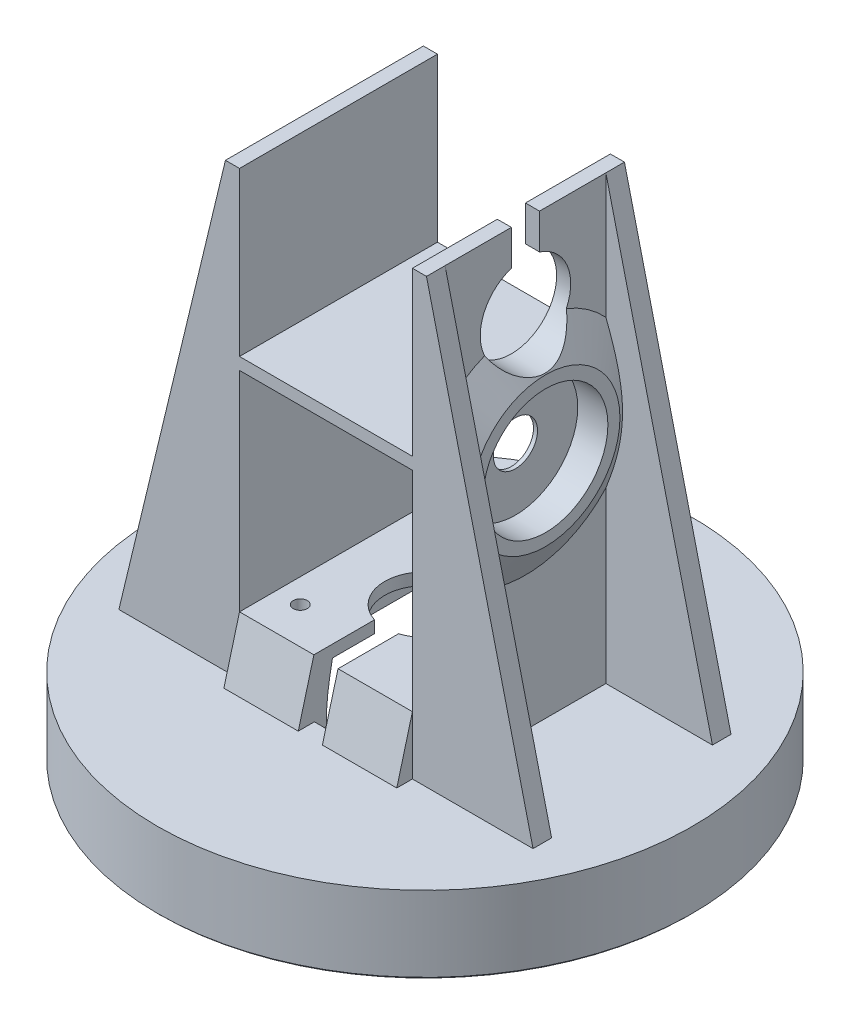
SolidWorks part; units mm, degrees
material "ABS"
ref_plane "Front Plane" through (0, 0, 0) normal (0, 0, 1) x (1, 0, 0)
ref_plane "Top Plane" through (0, 0, 0) normal (0, 1, 0) x (1, 0, 0)
ref_plane "Right Plane" through (0, 0, 0) normal (1, 0, 0) x (0, 0, -1)
sketch "Sketch1" plane through (0, 0, 0) normal (0, 1, 0) x (1, 0, 0)
  circle A0 centre (0, 0) radius 62.775 construction
  circle A1 centre (0, 0) radius 63.525
  circle A2 centre (0, 0) radius 66.525
  dimension "D1" = 125.55
  dimension "D2" = 0.75
  dimension "D3" = 3
extrude "Boss-Extrude1" add sketch "Sketch1" along normal blind 16.75
sketch "Sketch2" plane through (0, 16.75, 0) normal (0, 1, 0) x (1, 0, 0)
  circle A0 centre (0, 0) radius 66.525
  circle A1 centre (0, 0) radius 66.525 construction
extrude "Boss-Extrude2" add sketch "Sketch2" along normal blind 2.5
chamfer "Chamfer1" distance 0.5 angle 45 2 edges at (0, 0, 63.525) (0, 0, 66.525)
sketch "Sketch3" plane through (0, 16.75, 0) normal (0, -1, 0) x (1, 0, 0)
  line L0 (0, 37.5) -> (0, -37.5) construction
  line L1 (37.5, 0) -> (-37.5, 0) construction
  circle A0 centre (0, 37.5) radius 3
  circle A1 centre (37.5, 0) radius 3
  circle A2 centre (0, -37.5) radius 3
  circle A3 centre (-37.5, 0) radius 3
  point P8 (0, 0)
  point P9 (57.1447, 0)
  point P11 (0, 0)
  point P12 (0, 0)
  dimension "D1" = 6
  dimension "D2" = 75
extrude "Boss-Extrude3" add sketch "Sketch3" along normal blind 4
chamfer "Chamfer2" distance 0.5 angle 45 4 edges at (37.5, 16.75, 3) (0, 16.75, -34.5) (-37.5, 16.75, 3) (0, 16.75, 40.5)
sketch "Sketch4" plane through (0, 19.25, 0) normal (0, 1, 0) x (1, 0, 0)
  line L1 (-15.5, -15.5) -> (15.5, -15.5) construction
  line L2 (-15.5, -15.5) -> (-15.5, 15.5) construction
  line L3 (-15.5, 15.5) -> (15.5, 15.5) construction
  line L4 (15.5, -15.5) -> (15.5, 15.5) construction
  line L5 (-15.5, -15.5) -> (15.5, 15.5) construction
  line L6 (-15.5, 15.5) -> (15.5, -15.5) construction
  line L7 (-21.5, -21.5) -> (21.5, -21.5)
  line L8 (-21.5, -21.5) -> (-21.5, 21.5)
  line L9 (-21.5, 21.5) -> (21.5, 21.5)
  line L10 (21.5, -21.5) -> (21.5, 21.5)
  line L11 (-21.5, -21.5) -> (21.5, 21.5) construction
  line L12 (-21.5, 21.5) -> (21.5, -21.5) construction
  point P1 (0, 0)
  point P6 (0, 0)
  dimension "D1" = 31
  dimension "D2" = 6
extrude "Cut-Extrude1" cut sketch "Sketch4" against normal up to next
sketch "Sketch5" plane through (0, 19.25, 0) normal (0, 1, 0) x (1, 0, 0)
  line L0 (-21.5, 21.5) -> (21.5, 21.5)
  line L1 (-21.5, 21.5) -> (-21.5, 24.5)
  line L2 (21.5, 21.5) -> (21.5, 24.5)
  line L3 (-21.5, 24.5) -> (21.5, 24.5)
  line L4 (21.5, -21.5) -> (-21.5, -21.5)
  line L5 (21.5, -21.5) -> (21.5, -24.5)
  line L6 (-21.5, -21.5) -> (-21.5, -24.5)
  line L7 (21.5, -24.5) -> (-21.5, -24.5)
  dimension "D1" = 3
extrude "Boss-Extrude4" add sketch "Sketch5" along normal blind 14.5
sketch "Sketch6" plane through (0, 33.75, 0) normal (0, 1, 0) x (1, 0, 0)
  line L0 (-21.5, 24.5) -> (-21.5, -24.5)
  line L1 (-21.5, 24.5) -> (21.5, 24.5)
  line L2 (-21.5, -24.5) -> (21.5, -24.5)
  line L3 (21.5, 24.5) -> (21.5, -24.5)
  line L4 (-21.5, -24.5) -> (21.5, -24.5) construction
  point P0 (15.586, -24.5)
extrude "Boss-Extrude5" add sketch "Sketch6" against normal blind 3
sketch "Sketch7" plane through (0, 33.75, 0) normal (0, 1, 0) x (1, 0, 0)
  line L0 (-3, -24.5) -> (-3, -9.5394)
  line L1 (-15.5, -15.5) -> (15.5, -15.5) construction
  line L2 (-15.5, -15.5) -> (-15.5, 15.5) construction
  line L3 (-15.5, 15.5) -> (15.5, 15.5) construction
  line L4 (15.5, -15.5) -> (15.5, 15.5) construction
  line L5 (-15.5, -15.5) -> (15.5, 15.5) construction
  line L6 (-15.5, 15.5) -> (15.5, -15.5) construction
  line L8 (3, -9.5394) -> (3, -24.5)
  line L9 (3, -24.5) -> (-3, -24.5)
  line L10 (-21.5, -24.5) -> (21.5, -24.5) construction
  circle A0 centre (15.5, 15.5) radius 1.75
  circle A1 centre (-15.5, 15.5) radius 1.75
  circle A2 centre (-15.5, -15.5) radius 1.75
  circle A3 centre (15.5, -15.5) radius 1.75
  arc A4 (3, -9.5394) -> (-3, -9.5394) centre (0, 0) ccw
  point P0 (0, 0)
  point P14 (0, 0)
  point P15 (0, 0)
  point P18 (-3.952, -24.5)
  point P21 (0, -24.5)
  dimension "D1" = 3.5
  dimension "D3" = 20
  dimension "D2" = 31
  dimension "D4" = 6
extrude "Cut-Extrude2" cut sketch "Sketch7" against normal up to next
chamfer "Chamfer3" distance 4 angle 75 3 edges at (12.25, 19.25, 24.5) (-12.25, 19.25, 24.5) (0, 19.25, -24.5) first distance on face at (0, 19.25, 66.525)
chamfer "Chamfer5" distance 1.5 angle 80 3 edges at (0, 30.75, -21.5) (12.25, 30.75, 21.5) (-12.25, 30.75, 21.5) first distance on face at (0, 30.75, 5.3174)
fillet "Fillet1" radius 50 3 edges at (-12.25, 22.2431, 21.5) (12.25, 22.2431, 21.5) (0, 22.2431, -21.5)
ref_plane "Plane1" through (0, 0, -20) normal (0, 0, 1) x (1, 0, 0)
sketch "Sketch9" plane through (0, 0, -20) normal (0, 0, 1) x (1, 0, 0)
  line L0 (21.5, 19.25) -> (21.5, 129.25)
  line L1 (21.5, 129.25) -> (25, 129.25)
  line L2 (25, 129.25) -> (51.5, 19.25)
  line L3 (66.525, 19.25) -> (-66.525, 19.25) construction
  line L4 (51.5, 19.25) -> (21.5, 19.25)
  dimension "D1" = 3.5
  dimension "D2" = 30
  dimension "D3" = 110
extrude "Boss-Extrude6" add sketch "Sketch9" against normal up to vertex (4.6147 mm away) up to point (21.5, 33.75, -24.6147)
mirror "Mirror3" about plane through (0, 0, 0) normal (0, 0, 1) of "Boss-Extrude6"
sketch "Sketch10" plane through (0, 19.25, 0) normal (0, 1, 0) x (1, 0, 0)
  line L0 (25, 20) -> (25, -20)
  line L1 (25, 20) -> (21.5, 20)
  line L2 (25, -20) -> (21.5, -20)
  line L3 (21.5, 20) -> (21.5, -20)
  line L4 (21.5, -24.6147) -> (21.5, -20) construction
  point P0 (0, 0)
extrude "Boss-Extrude7" add sketch "Sketch10" along normal up to surface (110 mm away) up to face at (23.25, 129.25, -22.3074)
sketch "Sketch11" plane through (21.5, 0, 0) normal (-1, 0, 0) x (0, 0, 1)
  line L0 (0, -18.5625) -> (0, 18.5625) construction
  line L1 (24.6147, 33.75) -> (-24.6147, 33.75) construction
  circle A0 centre (0, 79.75) radius 5.5
  dimension "D2" = 11
  dimension "D1" = 46
extrude "Cut-Extrude3" cut sketch "Sketch11" against normal up to next
sketch "Sketch12" plane through (25, 0, 0) normal (1, 0, 0) x (0, 0, -1)
  circle A0 centre (0, 79.75) radius 15.5
  dimension "D1" = 31
extrude "Cut-Extrude4" cut sketch "Sketch12" against normal blind 2.5
sketch "Sketch13" plane through (25, 0, 0) normal (1, 0, 0) x (0, 0, -1)
  circle A0 centre (0, 79.75) radius 15.5 construction
  circle A1 centre (0, 79.75) radius 15.5
  circle A2 centre (0, 79.75) radius 18.5
  dimension "D1" = 3
extrude "Boss-Extrude8" add sketch "Sketch13" along normal blind 5
mirror "Mirror4" about plane through (0, 0, 0) normal (1, 0, 0) of "Cut-Extrude3", "Mirror3", "Boss-Extrude7", "Cut-Extrude4", "Boss-Extrude8", "Boss-Extrude6"
chamfer "Chamfer7" distance 5 angle 60 2 edges at (-25, 79.75, 18.5) (25, 79.75, 18.5) first distance on face at (-30, 79.75, -18.5) first distance on face at (30, 79.75, -18.5)
sketch "Sketch14" plane through (0, 0, 24.6147) normal (0, 0, 1) x (1, 0, 0)
  line L0 (-21.5, 85.75) -> (21.5, 85.75)
  line L1 (-21.5, 85.75) -> (-21.5, 88.75)
  line L2 (21.5, 85.75) -> (21.5, 88.75)
  line L3 (-21.5, 88.75) -> (21.5, 88.75)
  line L4 (-21.5, 129.25) -> (-21.5, 33.75) construction
  line L5 (21.5, 129.25) -> (21.5, 33.75) construction
  line L6 (-21.5, 85.25) -> (21.5, 85.25) construction
  dimension "D1" = 3
  dimension "D2" = 0.5
extrude "Boss-Extrude9" add sketch "Sketch14" against normal up to surface (49.2295 mm away) up to face at (-28.2, 66.15, -24.6147)
sketch "Sketch15" plane through (21.5, 0, 0) normal (-1, 0, 0) x (0, 0, 1)
  line L0 (0, -71.0875) -> (0, 71.0875) construction
  line L1 (-3.5, 129.25) -> (-3.5, 120.4417)
  line L2 (20, 129.25) -> (-20, 129.25) construction
  line L3 (-3.5, 129.25) -> (3.5, 129.25)
  line L4 (3.5, 129.25) -> (3.5, 120.4417)
  arc A0 (-3.5, 120.4417) -> (3.5, 120.4417) centre (0, 109.75) ccw
  point P8 (0, 129.25)
  dimension "D1" = 22.5
  dimension "D2" = 7
  dimension "D3" = 19.5
extrude "Cut-Extrude5" cut sketch "Sketch15" against normal up to next
